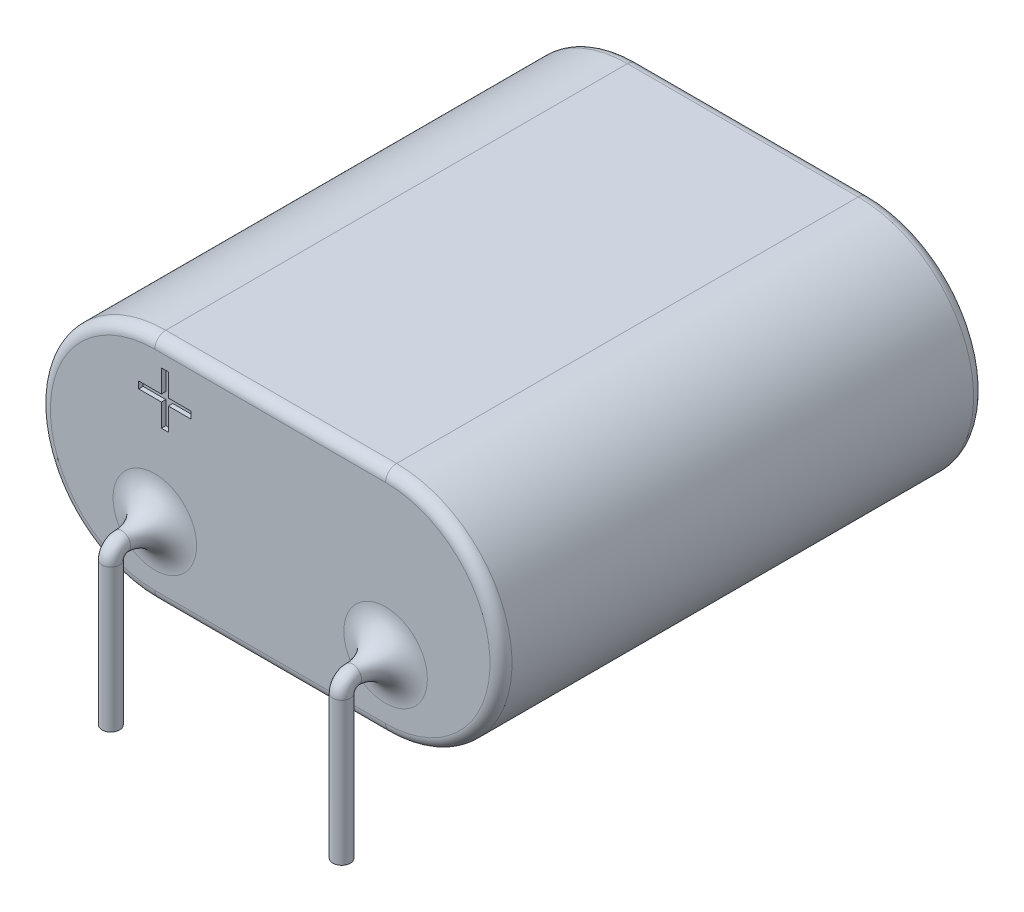
SolidWorks part; units mm, degrees
ref_plane "Front Plane" through (0, 0, 0) normal (0, 0, 1) x (1, 0, 0)
ref_plane "Top Plane" through (0, 0, 0) normal (0, 1, 0) x (1, 0, 0)
ref_plane "Right Plane" through (0, 0, 0) normal (1, 0, 0) x (0, 0, -1)
sketch "Sketch1" plane through (0, 0, 0) normal (0, 0, 1) x (1, 0, 0)
  line L0 (0, 5.25) -> (10.5, 5.25)
  line L1 (0, -5.25) -> (10.5, -5.25)
  arc A0 (0, 5.25) -> (0, -5.25) centre (0, 0) ccw
  arc A1 (10.5, -5.25) -> (10.5, 5.25) centre (10.5, 0) ccw
  point P9 (0, 0)
  point P10 (0, 0)
  dimension "D1" = 10.5
  dimension "D2" = 10.5
extrude "Boss-Extrude1" add sketch "Sketch1" against normal blind 22
sketch "Sketch2" plane through (0, 0, 0) normal (0, 0, 1) x (1, 0, 0)
  line L0 (0, 0) -> (0, 50000) construction
  line L1 (10.5, 0) -> (10.5, 50000) construction
  line L2 (0, -5.25) -> (10.5, -5.25) construction
  arc A0 (10.5, -5.25) -> (10.5, 5.25) centre (10.5, 0) ccw construction
  arc A1 (10.5, -5.25) -> (10.5, 5.25) centre (10.5, 0) ccw construction
  circle A2 centre (0, -2.05) radius 0.4
  circle A3 centre (10.5, -2.05) radius 0.4
  point P12 (0, 0)
  dimension "D1" = 0.8
  dimension "D2" = 3.2
ref_point "Point1"
ref_point "Point2"
ref_axis "Axis1" through (0, 0, 0) along (0, 1, 0)
ref_plane "Plane1" through (0, 0, 0) normal (1, 0, 0) x (0, 1, 0)
sketch "Sketch3" plane through (0, 0, 0) normal (1, 0, 0) x (0, 1, 0)
  line L0 (-2.05, 0) -> (-2.05, 1.5)
  line L1 (-2.55, 2) -> (-9.05, 2)
  arc A0 (-2.05, 1.5) -> (-2.55, 2) centre (-2.55, 1.5) ccw
  point P6 (-2.05, 2)
  dimension "D3" = 0.5
  dimension "D1" = 2
  dimension "D2" = 7
sweep "Sweep1" add profiles "Sketch2" path "Sketch3"
fillet "Fillet1" radius 1.5 2 edges at (10.9, -2.05, 0) (0.4, -2.05, 0)
fillet "Fillet2" radius 0.5 8 edges at (5.25, -5.25, -22) (15.75, 0, -22) (5.25, 5.25, -22) (-5.25, 0, -22) (5.25, 5.25, 0) (15.75, 0, 0) (5.25, -5.25, 0) (-5.25, 0, 0)
sketch "Sketch4" plane through (0, 0, 0) normal (0, 0, 1) x (1, 0, 0)
  line L1 (-1, 1.25) -> (3, 1.25) construction
  line L2 (0, 5.25) -> (10.5, 5.25) construction
  line L5 (0, -11) -> (0, 11) construction
  text T0 "+\r\n"
  dimension "D1" = 4
  dimension "D2" = 4
  dimension "D3" = 1
extrude "Cut-Extrude1" cut sketch "Sketch4" against normal blind 0.2
